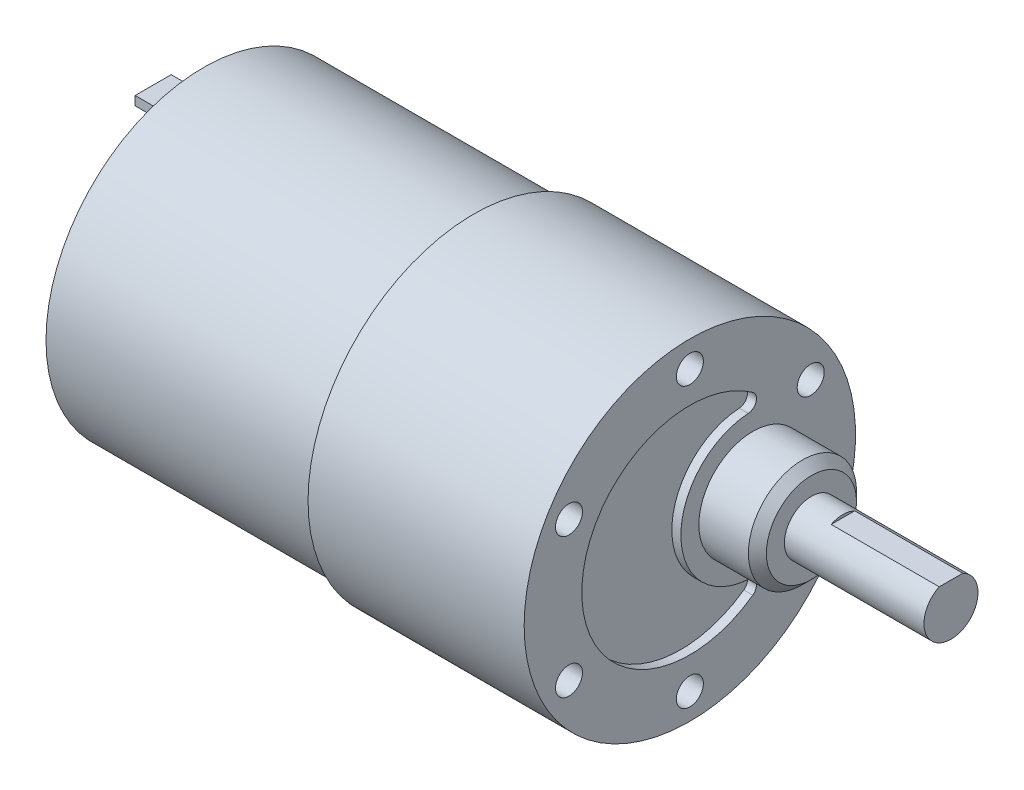
SolidWorks part; units mm, degrees
ref_plane "Plan de face" through (0, 0, 0) normal (0, 0, 1) x (1, 0, 0)
ref_plane "Plan de dessus" through (0, 0, 0) normal (0, 1, 0) x (1, 0, 0)
ref_plane "Plan de droite" through (0, 0, 0) normal (1, 0, 0) x (0, 0, -1)
sketch "Esquisse1" plane through (0, 0, 0) normal (0, 0, 1) x (1, 0, 0)
  line L0 (30, 17.5) -> (30, 18.4)
  line L1 (0, 0) -> (54, 0)
  line L2 (0, 0) -> (0, 17.5)
  line L3 (0, 17.5) -> (30, 17.5)
  line L7 (30, 18.4) -> (54, 18.4)
  line L8 (54, 0) -> (54, 18.4)
revolve "Révolution1" add sketch "Esquisse1" angle 360 about L1
sketch "Esquisse2" plane through (54, 0, 0) normal (1, 0, 0) x (0, 0, -1)
  circle A1 centre (0, 15.5) radius 1.5
  circle A2 centre (13.4234, 7.75) radius 1.5
  circle A3 centre (13.4234, -7.75) radius 1.5
  circle A4 centre (0, -15.5) radius 1.5
  circle A5 centre (-13.4234, -7.75) radius 1.5
  circle A6 centre (-13.4234, 7.75) radius 1.5
  dimension "D2" = 6
extrude "Enlèv. mat.-Extru.1" cut sketch "Esquisse2" against normal blind 10
sketch "Esquisse5" plane through (0, 0, 0) normal (0, 1, 0) x (1, 0, 0)
  line L1 (54, 7) -> (76, 7)
  line L2 (54, 7) -> (54, 13)
  line L3 (54, 13) -> (59.5, 13)
  line L4 (60.5, 12) -> (60.5, 10)
  line L7 (59.5, 13) -> (60.5, 12)
  line L9 (60.5, 10) -> (76, 10)
  line L10 (76, 7) -> (76, 10)
  point P1 (60.5, 13)
revolve "Révolution2" add sketch "Esquisse5" angle 360 about L1
sketch "Esquisse6" plane through (54, 0, 0) normal (1, 0, 0) x (0, 0, -1)
  circle A0 centre (0, 0) radius 12 construction
  circle A1 centre (7, 0) radius 8 construction
  arc A2 (6.988, 9.7554) -> (6.988, -9.7554) centre (0, 0) ccw
  arc A3 (6.4815, 7.9832) -> (6.4815, -7.9832) centre (7, 0) ccw
  arc A4 (6.988, -9.7554) -> (6.4815, -7.9832) centre (6.4181, -8.9598) ccw
  arc A5 (6.4815, 7.9832) -> (6.988, 9.7554) centre (6.4181, 8.9598) ccw
  dimension "D1" = 12
extrude "Enlèv. mat.-Extru.2" cut sketch "Esquisse6" against normal blind 1
sketch "Esquisse7" plane through (0, 0, 0) normal (0, 0, 1) x (1, 0, 0)
  line L0 (0, 17.5) -> (0, -17.5) construction
  line L1 (0, 12) -> (-5.6, 12)
  line L2 (0, 12) -> (0, 13)
  line L3 (0, 13) -> (-5.6, 13)
  line L4 (-5.6, 12) -> (-5.6, 13)
  line L5 (-5.6, 0) -> (0, 0) construction
  line L6 (-5.6, -12) -> (-5.6, -13)
  line L7 (0, -13) -> (-5.6, -13)
  line L8 (0, -12) -> (0, -13)
  line L9 (0, -12) -> (-5.6, -12)
  dimension "D1" = 12
extrude "Boss.-Extru.2" add sketch "Esquisse7" along normal blind 2 and the other way blind 2
sketch "Esquisse8" plane through (0, 0, 0) normal (0, 0, 1) x (1, 0, 0)
  line L1 (0, 0) -> (-1, 0)
  line L2 (0, 0) -> (0, 5)
  line L3 (0, 5) -> (-0.2, 5)
  line L4 (-1, 0) -> (-1, 4.2)
  arc A0 (-0.2, 5) -> (-1, 4.2) centre (-0.2, 4.2) ccw
  dimension "D1" = 0.8
revolve "Révolution3" add sketch "Esquisse8" angle 360 about L1
sketch "Esquisse9" plane through (76, 0, 0) normal (1, 0, 0) x (0, 0, -1)
  line L0 (5.6923, 2.7) -> (8.3077, 2.7)
  arc A0 (5.6923, 2.7) -> (8.3077, 2.7) centre (7, 0) ccw
  circle A1 centre (7, 0) radius 3 construction
  dimension "D1" = 2.7
extrude "Enlèv. mat.-Extru.3" cut sketch "Esquisse9" against normal blind 12 flip side to cut
